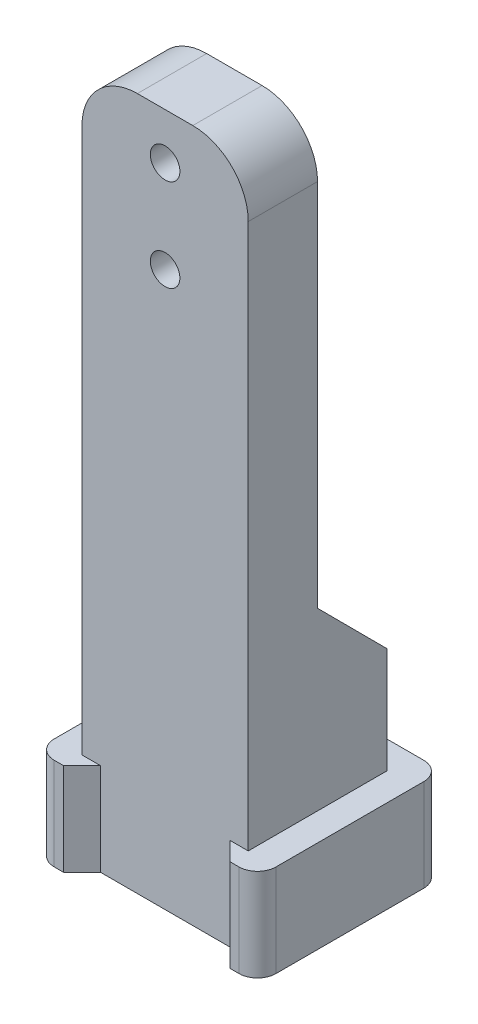
SolidWorks part; units mm, degrees
ref_plane "Front Plane" through (0, 0, 0) normal (0, 0, 1) x (1, 0, 0)
ref_plane "Top Plane" through (0, 0, 0) normal (0, 1, 0) x (1, 0, 0)
ref_plane "Right Plane" through (0, 0, 0) normal (1, 0, 0) x (0, 0, -1)
sketch "Sketch1" plane through (0, 0, 0) normal (0, 1, 0) x (1, 0, 0)
  line L1 (0, 0) -> (18, 0)
  line L2 (0, 0) -> (0, 15)
  line L3 (0, 15) -> (18, 15)
  line L4 (18, 0) -> (18, 15)
extrude "Boss-Extrude1" add sketch "Sketch1" along normal blind 75
sketch "Sketch2" plane through (0, 0, 0) normal (0, -1, 0) x (1, 0, 0)
  line L0 (9, 0) -> (9, -6)
  line L1 (0, 0) -> (18, 0) construction
  line L3 (9, -6) -> (14, -6)
  line L4 (9, -6) -> (4, -6)
  circle A0 centre (14, -6) radius 2
  circle A1 centre (4, -6) radius 2
extrude "Cut-Extrude1" cut sketch "Sketch2" against normal blind 12 contours A1 | A0 region at (14, 0, -4.0566) region at (2.0566, 0, -6)
sketch "Sketch3" plane through (18, 0, 0) normal (1, 0, 0) x (0, 0, -1)
  line L6 (7.5, 75) -> (7.5, 29)
  line L7 (0, 75) -> (15, 75) construction
  line L8 (7.5, 29) -> (15, 21.4721)
  line L9 (15, 75) -> (15, 0) construction
  line L10 (7.5, 75) -> (15, 75)
  line L11 (15, 75) -> (15, 21.4721)
extrude "Cut-Extrude2" cut sketch "Sketch3" against normal blind 48
sketch "Sketch4" plane through (0, 0, 0) normal (0, 0, 1) x (1, 0, 0)
  line L0 (9, 75) -> (9, 70)
  line L1 (0, 75) -> (18, 75) construction
  line L2 (9, 70) -> (9, 60)
  circle A0 centre (9, 70) radius 1.6
  circle A1 centre (9, 60) radius 1.6
  dimension "D1" = 10
extrude "Cut-Extrude3" cut sketch "Sketch4" against normal blind 48 contours L2 A0 L0 | L0 A0 L2 | A1 region at (9.6791, 70, 0) region at (10.0994, 61.0994, 0) region at (8.3209, 70, 0)
fillet "Fillet1" radius 6 2 edges at (0, 75, -3.75) (18, 75, -3.75)
sketch "Sketch5" plane through (0, 0, 0) normal (0, -1, 0) x (1, 0, 0)
  line L0 (0, 0) -> (0, 2)
  line L1 (0, 2) -> (-3, 2)
  line L2 (-3, 2) -> (-3, -18)
  line L3 (18, 0) -> (18, 2)
  line L4 (18, 2) -> (21, 2)
  line L5 (21, 2) -> (21, -18)
  line L6 (21, -18) -> (-3, -18)
  line L7 (0, 0) -> (0, -15)
  line L8 (0, -15) -> (18, -15)
  line L9 (18, -15) -> (18, 0)
extrude "Boss-Extrude2" add sketch "Sketch5" against normal blind 10
chamfer "Chamfer3" distance 2 angle 45 2 edges at (0, 5, 0) (18, 5, 0)
fillet "Fillet2" radius 2 4 edges at (21, 5, -18) (-3, 5, -18) (-3, 5, 2) (21, 5, 2)
